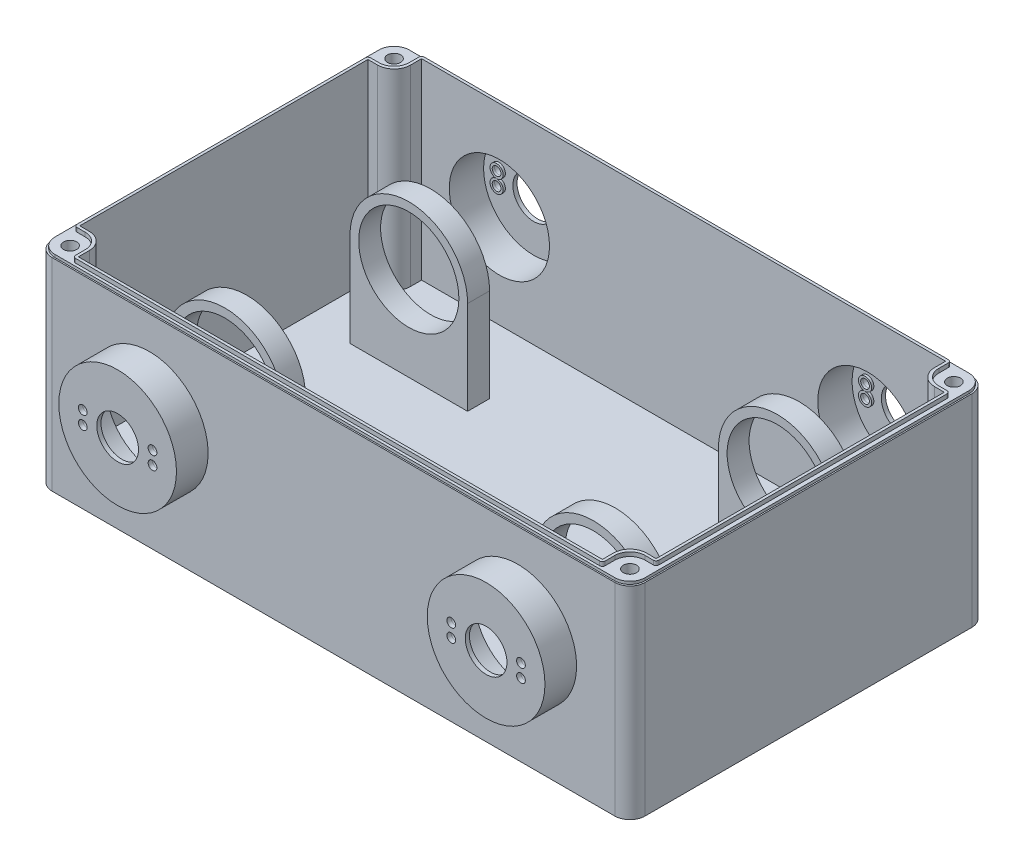
SolidWorks part; units mm, degrees
ref_plane "Front Plane" through (0, 0, 0) normal (0, 0, 1) x (1, 0, 0)
ref_plane "Top Plane" through (0, 0, 0) normal (0, 1, 0) x (1, 0, 0)
ref_plane "Right Plane" through (0, 0, 0) normal (1, 0, 0) x (0, 0, -1)
sketch "Sketch1" plane through (0, 0, 0) normal (0, 1, 0) x (1, 0, 0)
  line L1 (-107.95, 65) -> (107.95, 65)
  line L2 (-107.95, 65) -> (-107.95, -65)
  line L3 (-107.95, -65) -> (107.95, -65)
  line L4 (107.95, 65) -> (107.95, -65)
  line L5 (-107.95, 65) -> (107.95, -65) construction
  line L6 (-107.95, -65) -> (107.95, 65) construction
  point P0 (0, 0)
  point P6 (0, 0)
  point P14 (0, 0)
  dimension "D1" = 130
  dimension "D3" = 215.9
extrude "Boss-Extrude1" add sketch "Sketch1" along normal blind 73.7
sketch "Sketch2" plane through (0, 73.7, 0) normal (0, 1, 0) x (1, 0, 0)
  line L0 (-107.95, 65) -> (-107.95, -65) construction
  line L1 (-107.45, 64.5) -> (107.45, 64.5)
  line L2 (-107.45, 64.5) -> (-107.45, -64.5)
  line L3 (-107.45, -64.5) -> (107.45, -64.5)
  line L4 (107.45, 64.5) -> (107.45, -64.5)
  line L5 (-107.45, 64.5) -> (107.45, -64.5) construction
  line L6 (-107.45, -64.5) -> (107.45, 64.5) construction
  line L7 (107.95, 65) -> (-107.95, 65) construction
  point P0 (0, 0)
  dimension "D1" = 0.5
  dimension "D2" = 0.5
extrude "Boss-Extrude2" add sketch "Sketch2" along normal blind 1
fillet "Fillet1" radius 5.5118 4 edges at (107.45, 74.2, -64.5) (107.45, 74.2, 64.5) (-107.45, 74.2, 64.5) (-107.45, 74.2, -64.5)
fillet "Fillet2" radius 5.5118 4 edges at (-107.95, 36.85, 65) (107.95, 36.85, 65) (-107.95, 36.85, -65) (107.95, 36.85, -65)
hole_wizard "M4 Clearance Hole1" positions "Sketch5" profile "Sketch6" hole size "M4" standard "ANSI Metric" end condition through all
sketch "Sketch5" plane through (0, 74.7, 0) normal (0, 1, 0) x (1, 0, 0)
  line L0 (101.9382, 64.5) -> (-101.9382, 64.5) construction
  line L1 (107.45, -58.9882) -> (107.45, 58.9882) construction
  line L2 (107.45, -58.9882) -> (107.45, 58.9882) construction
  line L3 (-101.9382, -64.5) -> (101.9382, -64.5) construction
  point P0 (-101.9382, 58.9882)
  point P3 (-101.9382, -58.9882)
  point P6 (101.9382, -58.9882)
  point P9 (101.9382, 58.9882)
  dimension "D1" = 5.5118
  dimension "D2" = 5.5118
  dimension "D3" = 5.5118
  dimension "D4" = 5.5118
sketch "Sketch6" plane through (-101.9382, 74.7, -58.9882) normal (1, 0, 0) x (0, 0, 1)
  line L0 (0, 0) -> (0, 74.7)
  line L1 (0, 74.7) -> (2.4, 74.7)
  line L2 (2.4, 74.7) -> (2.4, 0)
  line L5 (2.4, 0) -> (0, 0)
  line L11 (0, -6.35) -> (0, 107.95) construction
  dimension "Thru Hole Dia." = 4.8
  dimension "Thru Hole Depth" = 74.7
sketch "Sketch7" plane through (0, 74.7, 0) normal (0, 1, 0) x (1, 0, 0)
  line L0 (102.4382, 65) -> (-102.4382, 65) construction
  line L1 (-105.95, 63.5) -> (105.95, 63.5)
  line L2 (-105.95, 63.5) -> (-105.95, -63.5)
  line L3 (-105.95, -63.5) -> (105.95, -63.5)
  line L4 (105.95, 63.5) -> (105.95, -63.5)
  line L5 (-105.95, 63.5) -> (105.95, -63.5) construction
  line L6 (-105.95, -63.5) -> (105.95, 63.5) construction
  line L7 (-105.95, -53.4764) -> (-101.9382, -53.4764)
  line L8 (-96.4264, 63.5) -> (-96.4264, 58.9882)
  line L9 (-105.95, 53.4764) -> (-101.9382, 53.4764)
  line L10 (-96.4264, -63.5) -> (-96.4264, -58.9882)
  line L12 (96.4264, -63.5) -> (96.4264, -58.9882)
  line L13 (105.95, -53.4764) -> (101.9382, -53.4764)
  line L14 (96.4264, 63.5) -> (96.4264, 58.9882)
  line L15 (105.95, 53.4764) -> (101.9382, 53.4764)
  line L16 (-107.45, 58.9882) -> (-107.45, -58.9882) construction
  circle A6 centre (101.9382, 58.9882) radius 5.5118
  circle A7 centre (101.9382, -58.9882) radius 5.5118
  circle A8 centre (-101.9382, 58.9882) radius 5.5118
  circle A9 centre (-101.9382, -58.9882) radius 5.5118
  point P0 (0, 0)
  dimension "D3" = 11.0236
  dimension "D4" = 11.0236
  dimension "D5" = 11.0236
  dimension "D6" = 11.0236
  dimension "D1" = 1.5
  dimension "D2" = 1.5
extrude "Boss-Extrude3" add sketch "Sketch7" along normal blind 1.5 contours A6 L1 A8 L2 A9 L3 L4 region at (0, 74.7, 0)
fillet "Fillet3" radius 1 8 edges at (96.4264, 75.45, 63.5) (105.95, 75.45, 53.4764) (105.95, 75.45, -53.4764) (96.4264, 75.45, -63.5) (-105.95, 75.45, -53.4764) (-96.4264, 75.45, -63.5) (-105.95, 75.45, 53.4764) (-96.4264, 75.45, 63.5)
sketch "Sketch8" plane through (0, 76.2, 0) normal (0, 1, 0) x (1, 0, 0)
  line L0 (-95.4264, -63.5) -> (95.4264, -63.5) construction
  line L1 (-104.95, 62.5) -> (104.95, 62.5)
  line L2 (-104.95, 62.5) -> (-104.95, -62.5)
  line L3 (-104.95, -62.5) -> (104.95, -62.5)
  line L4 (104.95, 62.5) -> (104.95, -62.5)
  line L5 (-104.95, 62.5) -> (104.95, -62.5) construction
  line L6 (-104.95, -62.5) -> (104.95, 62.5) construction
  line L7 (-105.95, 52.4764) -> (-105.95, -52.4764) construction
  line L8 (-96.4264, 62.5) -> (-96.4264, 58.9882) construction
  line L9 (-104.95, 52.4764) -> (-101.4264, 52.4764)
  line L10 (-104.95, -52.4764) -> (-101.4264, -52.4764)
  line L12 (95.4264, 62.5) -> (95.4264, 58.4764)
  line L13 (101.4264, 52.4764) -> (104.95, 52.4764)
  line L14 (95.4264, -62.5) -> (95.4264, -58.4764)
  line L15 (101.4264, -52.4764) -> (104.95, -52.4764)
  line L16 (104.95, -53.4764) -> (101.9382, -53.4764) construction
  line L17 (96.4264, -62.5) -> (96.4264, -58.9882) construction
  line L24 (-95.4264, 58.4764) -> (-95.4264, 62.5)
  line L25 (104.95, 53.4764) -> (101.9382, 53.4764) construction
  line L26 (96.4264, 62.5) -> (96.4264, 58.9882) construction
  line L29 (-95.4264, -58.4764) -> (-95.4264, -62.5)
  line L30 (-96.4264, -62.5) -> (-96.4264, -58.9882) construction
  arc A0 (-95.4264, 58.4764) -> (-101.4264, 52.4764) centre (-101.4264, 58.4764) cw
  arc A1 (-95.4264, -58.4764) -> (-101.4264, -52.4764) centre (-101.4264, -58.4764) ccw
  arc A2 (95.4264, 58.4764) -> (101.4264, 52.4764) centre (101.4264, 58.4764) ccw
  arc A3 (95.4264, -58.4764) -> (101.4264, -52.4764) centre (101.4264, -58.4764) cw
  point P0 (0, 0)
  point P18 (95.4264, 62.5)
  point P19 (104.95, 52.4764)
  dimension "D3" = 6
  dimension "D4" = 6
  dimension "D5" = 6
  dimension "D6" = 6
  dimension "D7" = 1
  dimension "D1" = 1
  dimension "D2" = 1
  dimension "D8" = 1
  dimension "D10" = 1
  dimension "D11" = 1
  dimension "D12" = 1
  dimension "D13" = 1
extrude "Cut-Extrude2" cut sketch "Sketch8" against normal blind 69.85 contours L4 L13 A2 L12 L1 L2 L3 region at (0, 76.2, 0)
sketch "Sketch9" plane through (0, 0, 65) normal (0, 0, 1) x (1, 0, 0)
  line L0 (-102.4382, 0) -> (102.4382, 0) construction
  line L2 (-102.4382, 73.7) -> (-102.4382, 0) construction
  line L3 (102.4382, 0) -> (102.4382, 73.7) construction
  circle A0 centre (-67.0941, 40.35) radius 18.25
  circle A1 centre (67.0941, 40.35) radius 18.25
  dimension "D2" = 36.5
  dimension "D1" = 40.35
  dimension "D4" = 35.3441
  dimension "D5" = 35.3441
extrude "Cut-Extrude3" cut sketch "Sketch9" against normal through all
sketch "Sketch10" plane through (0, 0, 65) normal (0, 0, 1) x (1, 0, 0)
  circle A0 centre (-67.0941, 40.35) radius 21.425
  circle A1 centre (67.0941, 40.35) radius 21.425
  circle A2 centre (-67.0941, 40.35) radius 18.25 construction
  circle A3 centre (67.0941, 40.35) radius 18.25 construction
  circle A4 centre (-67.0941, 40.35) radius 18.25
  circle A5 centre (67.0941, 40.35) radius 18.25
  dimension "D1" = 3.175
  dimension "D2" = 3.175
  dimension "D3" = 36.5
  dimension "D4" = 36.5
extrude "Boss-Extrude5" add sketch "Sketch10" along normal blind 10
sketch "Sketch11" plane through (0, 0, 75) normal (0, 0, 1) x (1, 0, 0)
  circle A2 centre (-67.0941, 40.35) radius 7.59
  circle A4 centre (67.0941, 40.35) radius 7.59
  circle A5 centre (-67.0941, 40.35) radius 21.425
  circle A6 centre (67.0941, 40.35) radius 21.425
  dimension "D1" = 15.18
  dimension "D2" = 15.18
extrude "Boss-Extrude6" add sketch "Sketch11" along normal blind 1.525
sketch "Sketch12" plane through (0, 0, -65) normal (0, 0, -1) x (-1, 0, 0)
  circle A0 centre (-67.0941, 40.35) radius 21.425
  circle A1 centre (67.0941, 40.35) radius 21.425
  circle A2 centre (67.0941, 40.35) radius 18.25
  circle A3 centre (-67.0941, 40.35) radius 18.25
  dimension "D1" = 3.175
  dimension "D2" = 3.175
  dimension "D3" = 36.5
  dimension "D4" = 36.5
extrude "Boss-Extrude7" add sketch "Sketch12" along normal blind 10
sketch "Sketch13" plane through (0, 0, -75) normal (0, 0, -1) x (-1, 0, 0)
  circle A1 centre (-67.0941, 40.35) radius 7.59
  circle A3 centre (67.0941, 40.35) radius 7.59
  circle A5 centre (-67.0941, 40.35) radius 21.425
  circle A6 centre (67.0941, 40.35) radius 21.425
  dimension "D1" = 15.18
  dimension "D2" = 15.18
extrude "Boss-Extrude8" add sketch "Sketch13" along normal blind 1.525
sketch "Sketch14" plane through (0, 0, -62.5) normal (0, 0, 1) x (1, 0, 0)
  circle A0 centre (-67.0941, 40.35) radius 18.25
  circle A1 centre (-67.0941, 40.35) radius 21.425
  circle A3 centre (67.0941, 40.35) radius 18.25
  circle A4 centre (67.0941, 40.35) radius 21.425
  dimension "D1" = 3.175
  dimension "D2" = 3.175
  dimension "D3" = 36.5
  dimension "D4" = 36.5
extrude "Boss-Extrude9" add sketch "Sketch14" along normal blind 8 from offset 25 separate body
sketch "Sketch15" plane through (0, 0, -29.5) normal (0, 0, 1) x (1, 0, 0)
  line L0 (-95.4264, 6.35) -> (95.4264, 6.35) construction
  line L1 (-88.5191, 40.35) -> (-45.6691, 40.35)
  line L2 (-45.6691, 40.35) -> (-45.6691, 6.35)
  line L3 (-45.6691, 6.35) -> (-88.5191, 6.35)
  line L4 (-88.5191, 6.35) -> (-88.5191, 40.35)
  line L9 (45.6691, 40.35) -> (88.5191, 40.35)
  line L10 (88.5191, 40.35) -> (88.5191, 6.35)
  line L11 (88.5191, 6.35) -> (45.6691, 6.35)
  line L12 (45.6691, 6.35) -> (45.6691, 40.35)
  circle A0 centre (-67.0941, 40.35) radius 21.425 construction
  circle A1 centre (-67.0941, 40.35) radius 21.425
  circle A2 centre (67.0941, 40.35) radius 21.425
  point P0 (-88.5191, 40.35)
  point P1 (-88.5191, 40.35)
  point P4 (-45.6691, 6.35)
  point P5 (-88.5191, 40.35)
  point P8 (-88.5191, 6.35)
  point P19 (45.6691, 40.35)
  point P20 (88.5191, 40.35)
  point P21 (88.5191, 6.35)
  point P22 (45.6691, 6.35)
  circle M1 centre (-67.0941, 40.35) radius 21.425
extrude "Boss-Extrude11" add sketch "Sketch15" against normal blind 8 contours A2 L12 L11 L10 | L4 L3 L2 M1 region at (-67.0941, 15.6022, -29.5) region at (67.0941, 15.6022, -29.5)
sketch "Sketch16" plane through (0, 0, 62.5) normal (0, 0, -1) x (-1, 0, 0)
  circle A0 centre (-67.0941, 40.35) radius 18.25
  circle A1 centre (-67.0941, 40.35) radius 21.425
  circle A2 centre (67.0941, 40.35) radius 18.25
  circle A3 centre (67.0941, 40.35) radius 21.425
  dimension "D1" = 3.175
  dimension "D2" = 3.175
  dimension "D3" = 36.5
  dimension "D4" = 36.5
extrude "Boss-Extrude12" add sketch "Sketch16" along normal blind 8 from offset 25 separate body
sketch "Sketch17" plane through (0, 0, 29.5) normal (0, 0, -1) x (-1, 0, 0)
  line L0 (95.4264, 6.35) -> (-95.4264, 6.35) construction
  line L1 (-88.5191, 40.35) -> (-45.6691, 40.35)
  line L2 (-45.6691, 40.35) -> (-45.6691, 6.35)
  line L3 (-45.6691, 6.35) -> (-88.5191, 6.35)
  line L4 (-88.5191, 6.35) -> (-88.5191, 40.35)
  line L5 (88.5191, 40.35) -> (88.5191, 6.35)
  line L6 (88.5191, 6.35) -> (45.6691, 6.35)
  line L7 (45.6691, 6.35) -> (45.6691, 40.35)
  line L8 (45.6691, 40.35) -> (88.5191, 40.35)
  circle A0 centre (-67.0941, 40.35) radius 21.425 construction
  circle A1 centre (67.0941, 40.35) radius 21.425 construction
  circle A2 centre (-67.0941, 40.35) radius 21.425
  circle A3 centre (67.0941, 40.35) radius 21.425
  point P0 (-88.5191, 40.35)
  point P1 (-45.6691, 40.35)
  point P4 (-88.5191, 6.35)
  point P5 (-45.6691, 6.35)
  point P8 (88.5191, 40.35)
  point P9 (88.5191, 6.35)
  point P12 (45.6691, 6.35)
  point P13 (45.6691, 40.35)
  circle M1 centre (-67.0941, 40.35) radius 21.425
extrude "Boss-Extrude13" add sketch "Sketch17" against normal blind 8 contours L4 L3 L2 M1 | A3 L5 L6 L7 region at (67.0941, 15.6022, 29.5) region at (-67.0941, 15.6022, 29.5)
sketch "Sketch18" plane through (0, 0, -76.525) normal (0, 0, -1) x (-1, 0, 0)
  circle A0 centre (-79.7941, 42.7313) radius 1.5875
  circle A1 centre (-79.7941, 37.9688) radius 1.5875
  circle A2 centre (-54.3941, 42.7313) radius 1.5875
  circle A3 centre (-54.3941, 37.9688) radius 1.5875
  circle A4 centre (-67.0941, 40.35) radius 7.59 construction
  dimension "D1" = 3.175
  dimension "D2" = 12.7
  dimension "D3" = 12.7
  dimension "D4" = 4.7625
  dimension "D5" = 2.3813
extrude "Cut-Extrude4" cut sketch "Sketch18" against normal through all
mirror "Mirror1" about plane through (0, 0, 0) normal (1, 0, 0) of "Cut-Extrude4"
sketch "Sketch21" plane through (0, 0, -75) normal (0, 0, 1) x (1, 0, 0)
  circle A0 centre (54.3941, 42.7313) radius 1.5875
  circle A1 centre (54.3941, 42.7313) radius 2.3875
  circle A2 centre (54.3941, 37.9688) radius 1.5875
  circle A3 centre (54.3941, 37.9688) radius 2.3875
  circle A4 centre (79.7941, 42.7313) radius 1.5875
  circle A5 centre (79.7941, 37.9688) radius 1.5875
  circle A6 centre (79.7941, 42.7313) radius 2.3875
  circle A7 centre (79.7941, 37.9688) radius 2.3875
  circle M1 centre (79.7941, 37.9688) radius 1.5875
  circle M2 centre (54.3941, 42.7313) radius 1.5875
  circle M3 centre (54.3941, 37.9688) radius 1.5875
  circle M4 centre (79.7941, 42.7313) radius 1.5875
  dimension "D1" = 0.8
extrude "Boss-Extrude14" add sketch "Sketch21" along normal blind 0.825 separate body contours A7 A6 M4 | A6 A7 M1 | A3 A1 M2 | A1 A3 M3 region at (56.0929, 41.1512, -75) region at (54.3941, 40.2763, -75) region at (81.4929, 41.1512, -75) region at (79.7941, 40.2763, -75)
sketch "Sketch22" plane through (0, 0, -75) normal (0, 0, 1) x (1, 0, 0)
  circle A0 centre (-79.7941, 42.7313) radius 1.5875
  circle A1 centre (-79.7941, 42.7313) radius 2.3875
  circle A2 centre (-79.7941, 37.9688) radius 1.5875
  circle A3 centre (-79.7941, 37.9688) radius 2.3875
  circle A4 centre (-54.3941, 42.7313) radius 1.5875
  circle A5 centre (-54.3941, 42.7313) radius 2.3875
  circle A6 centre (-54.3941, 37.9688) radius 1.5875
  circle A7 centre (-54.3941, 37.9688) radius 2.3875
  circle M1 centre (-79.7941, 37.9688) radius 1.5875
  circle M2 centre (-54.3941, 42.7313) radius 1.5875
  circle M3 centre (-54.3941, 37.9688) radius 1.5875
  circle M4 centre (-79.7941, 42.7313) radius 1.5875
  dimension "D1" = 0.8
extrude "Boss-Extrude15" add sketch "Sketch22" along normal blind 0.825 separate body contours A3 A1 M4 | A1 A3 M1 | A7 A5 M2 | A5 A7 M3 region at (-78.0953, 41.1512, -75) region at (-79.7941, 40.2763, -75) region at (-52.6953, 41.1512, -75) region at (-54.3941, 40.2763, -75)
sketch "Sketch23" plane through (0, 0, 75) normal (0, 0, -1) x (-1, 0, 0)
  circle A0 centre (-79.7941, 42.7313) radius 1.5875
  circle A1 centre (-79.7941, 42.7313) radius 2.3875
  circle A2 centre (-79.7941, 37.9688) radius 1.5875
  circle A3 centre (-79.7941, 37.9688) radius 2.3875
  circle A4 centre (-54.3941, 42.7313) radius 1.5875
  circle A5 centre (-54.3941, 42.7313) radius 2.3875
  circle A6 centre (-54.3941, 37.9688) radius 1.5875
  circle A7 centre (-54.3941, 37.9688) radius 2.3875
  circle M1 centre (-79.7941, 37.9688) radius 1.5875
  circle M2 centre (-54.3941, 42.7313) radius 1.5875
  circle M3 centre (-54.3941, 37.9688) radius 1.5875
  circle M4 centre (-79.7941, 42.7313) radius 1.5875
  dimension "D1" = 0.8
extrude "Boss-Extrude16" add sketch "Sketch23" along normal blind 0.825 separate body contours A1 A3 M1 | A3 A1 M4 | A7 A5 M2 | A5 A7 M3 region at (78.0953, 41.1512, 75) region at (79.7941, 40.2763, 75) region at (52.6953, 41.1512, 75) region at (54.3941, 40.2763, 75)
sketch "Sketch24" plane through (0, 0, 75) normal (0, 0, -1) x (-1, 0, 0)
  circle A0 centre (54.3941, 42.7313) radius 1.5875
  circle A1 centre (54.3941, 42.7313) radius 2.3875
  circle A2 centre (54.3941, 37.9688) radius 1.5875
  circle A3 centre (54.3941, 37.9688) radius 2.3875
  circle A4 centre (79.7941, 42.7313) radius 1.5875
  circle A5 centre (79.7941, 42.7313) radius 2.3875
  circle A6 centre (79.7941, 37.9688) radius 1.5875
  circle A7 centre (79.7941, 37.9688) radius 2.3875
  circle M1 centre (79.7941, 37.9688) radius 1.5875
  circle M2 centre (54.3941, 42.7313) radius 1.5875
  circle M3 centre (54.3941, 37.9688) radius 1.5875
  circle M4 centre (79.7941, 42.7313) radius 1.5875
  dimension "D1" = 0.8
extrude "Boss-Extrude18" add sketch "Sketch24" along normal blind 0.825 separate body contours A3 A1 M2 | A1 A3 M3 | A7 A5 M4 | A5 A7 M1 region at (-56.0929, 41.1512, 75) region at (-54.3941, 40.2763, 75) region at (-81.4929, 41.1512, 75) region at (-79.7941, 40.2763, 75)
